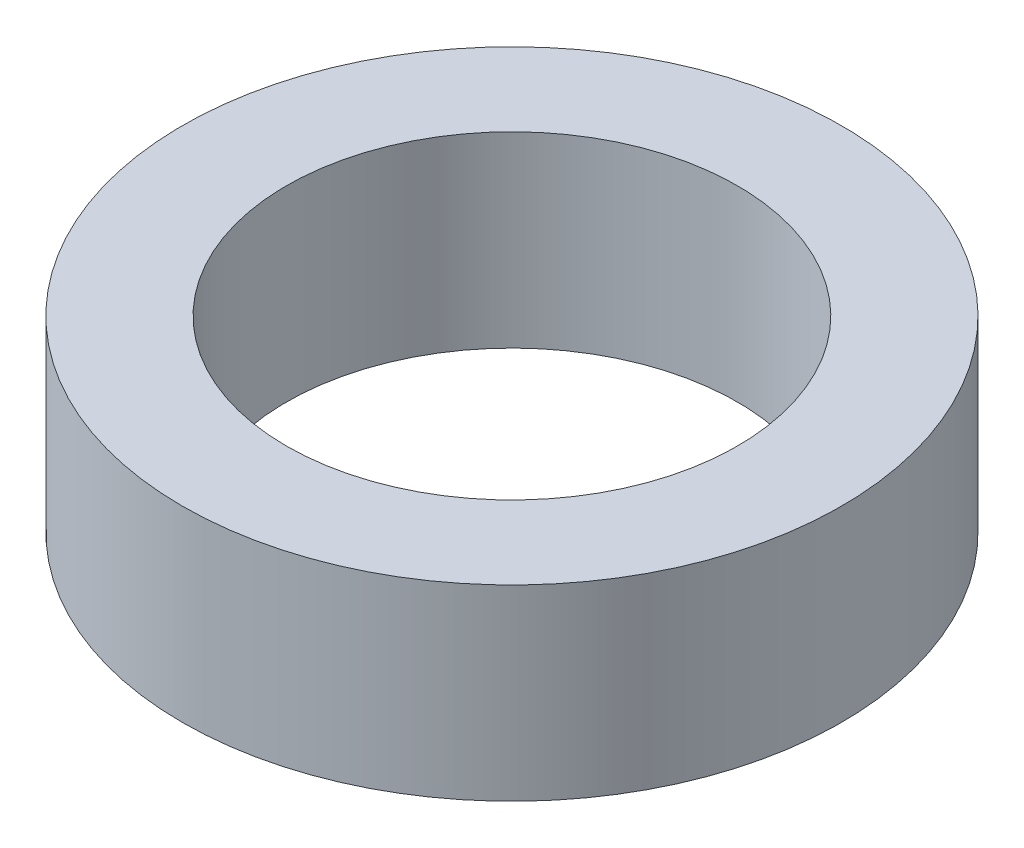
SolidWorks part; units mm, degrees
ref_plane "Front Plane" through (0, 0, 0) normal (0, 0, 1) x (1, 0, 0)
ref_plane "Top Plane" through (0, 0, 0) normal (0, 1, 0) x (1, 0, 0)
ref_plane "Right Plane" through (0, 0, 0) normal (1, 0, 0) x (0, 0, -1)
sketch "Sketch1" plane through (0, 0, 0) normal (0, 1, 0) x (1, 0, 0)
  circle A0 centre (0, 0) radius 47.5
  dimension "FLANGE_OD" = 95
extrude "Boss-Extrude1" add sketch "Sketch1" along normal blind 27
sketch "Sketch2" plane through (0, 0, 0) normal (0, 1, 0) x (1, 0, 0)
  circle A0 centre (0, 0) radius 32.5
  dimension "BORE_D" = 65
extrude "Cut-Extrude1" cut sketch "Sketch2" along normal through all
sketch "Sketch3" plane through (0, 27, 0) normal (0, 1, 0) x (1, 0, 0)
  circle A0 centre (0, 0) radius 19.4537 construction
  circle A1 centre (-19.4537, 0) radius 1.5311
  dimension "BOLT_D" = 3.0622
  dimension "BOLT_PCD" = 38.9074
extrude "Cut-Extrude2" cut sketch "Sketch3" against normal blind 19.5331 rebuild error yes
pattern_circular "CirPattern1" count 3 over 360 rebuild error yes
